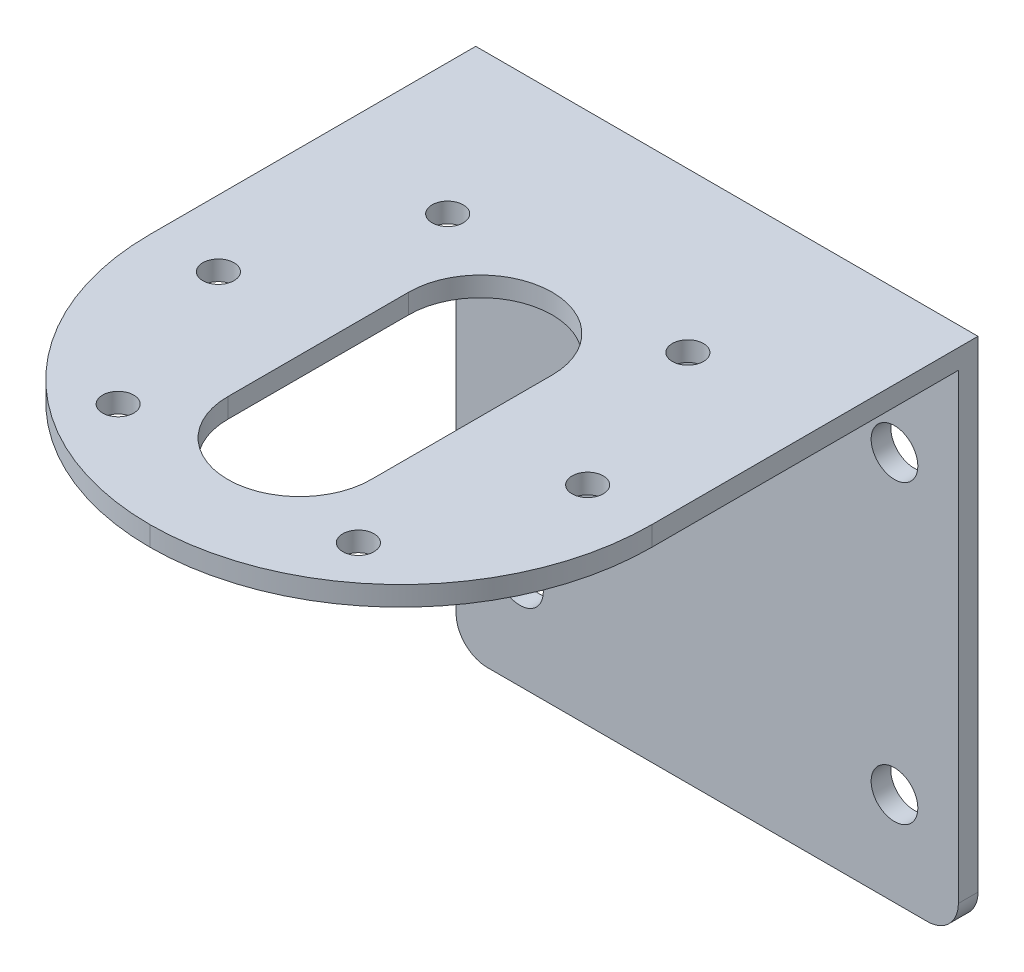
SolidWorks part; units mm, degrees
ref_plane "Front Plane" through (0, 0, 0) normal (0, 0, 1) x (1, 0, 0)
ref_plane "Top Plane" through (0, 0, 0) normal (0, 1, 0) x (1, 0, 0)
ref_plane "Right Plane" through (0, 0, 0) normal (1, 0, 0) x (0, 0, -1)
sketch "Sketch1" plane through (0, 0, 0) normal (0, 0, 1) x (1, 0, 0)
  line L1 (0, 0) -> (40.894, 0)
  line L2 (0, 0) -> (0, 40.132)
  line L3 (0, 40.132) -> (40.894, 40.132)
  line L4 (40.894, 0) -> (40.894, 40.132)
  dimension "D1" = 40.132
  dimension "D2" = 40.894
extrude "Boss-Extrude1" add sketch "Sketch1" along normal blind 1.6
sketch "Sketch2" plane through (0, 0, 1.6) normal (0, 0, 1) x (1, 0, 0)
  line L0 (40.894, 40.132) -> (0, 40.132) construction
  line L1 (0, 40.132) -> (0, 0) construction
  circle A0 centre (5.2, 31.732) radius 1.9
  circle A1 centre (5.2, 7.612) radius 1.9
  dimension "D1" = 3.8
  dimension "D2" = 8.4
  dimension "D3" = 5.2
  dimension "D4" = 5.2
  dimension "D5" = 24.12
extrude "Cut-Extrude1" cut sketch "Sketch2" against normal through all contours A1
sketch "Sketch3" plane through (0, 0, 1.6) normal (0, 0, 1) x (1, 0, 0)
extrude "Cut-Extrude2" cut sketch "Sketch2<3>" against normal through all
sketch "Sketch2<3>" plane through (0, 0, 1.6) normal (0, 0, 1) x (1, 0, 0) same geometry as "Sketch2"
ref_plane "Plane1" through (20.447, 0, 0) normal (-1, 0, 0) x (0, 0, 1)
mirror "Mirror2" about plane through (20.447, 0, 0) normal (-1, 0, 0) of "Cut-Extrude1", "Cut-Extrude2"
fillet "Fillet1" radius 2.54 2 edges at (40.894, 0, 0.8) (0, 0, 0.8)
sketch "Sketch5" plane through (0, 40.132, 0) normal (0, 1, 0) x (1, 0, 0)
  line L1 (40.894, 0) -> (0, 0)
  line L2 (40.894, 0) -> (40.894, -46.99)
  line L3 (40.894, -46.99) -> (0, -46.99)
  line L4 (0, 0) -> (0, -46.99)
  dimension "D1" = 46.99
extrude "Boss-Extrude2" add sketch "Sketch5" along normal blind 1.6
fillet "Fillet2" radius 20.447 2 edges at (0, 40.932, 46.99) (40.894, 40.932, 46.99)
sketch "Sketch6" plane through (0, 41.732, 0) normal (0, 1, 0) x (1, 0, 0)
  line L0 (40.894, 0) -> (0, 0) construction
  line L1 (40.894, -26.543) -> (40.894, 0) construction
  line L2 (30.226, -38.514) -> (30.226, -14.224) construction
  line L3 (30.226, -26.369) -> (40.8933, -26.369) construction
  circle A0 centre (30.226, -39.784) radius 1.27
  circle A1 centre (30.226, -12.954) radius 1.27
  circle A2 centre (35.48, -26.369) radius 1.27
  arc A3 (20.447, -46.99) -> (40.894, -26.543) centre (20.447, -26.543) ccw construction
  dimension "D1" = 2.54
  dimension "D2" = 12.954
  dimension "D3" = 10.668
  dimension "D4" = 26.83
  dimension "D5" = 5.414
extrude "Cut-Extrude3" cut sketch "Sketch6" against normal through all
mirror "Mirror3" about plane through (20.447, 0, 0) normal (-1, 0, 0) of "Cut-Extrude3"
sketch "Sketch7" plane through (0, 41.732, 0) normal (0, 1, 0) x (1, 0, 0)
  line L0 (20.447, -34.798) -> (20.447, -20.066) construction
  line L1 (20.447, 0.88) -> (20.447, -0.88) construction
  line L2 (14.605, -34.798) -> (14.605, -20.066)
  line L3 (26.289, -34.798) -> (26.289, -20.066)
  arc A0 (14.605, -34.798) -> (26.289, -34.798) centre (20.447, -34.798) ccw
  arc A1 (26.289, -20.066) -> (14.605, -20.066) centre (20.447, -20.066) ccw
  point P4 (20.447, -27.432)
  dimension "D1" = 5.842
  dimension "D2" = 14.732
  dimension "D3" = 12.192
extrude "Cut-Extrude4" cut sketch "Sketch7" against normal through all
equation "\"FoamCore\" = \".2\""
equation "\"MDF\" = \".2\""
equation "\"GMaterial\"= \".2\""
equation "\"PVCMountDiameter\" = \"0.5in\""
equation "\"PVCMountDistanceToEdge\" = \"0.5\""
equation "\"PVCThickness\" = \"0.13in\""
equation "\"BaseWidth\" = \"8in\""
equation "\"BaseLength\" = \"10in\""
equation "\"BallDiameter\" = \"38mm\""
equation "\"BaseGap\" = \"4in\""
equation "\"FunnelTopDiameter\" = \"8in\""
equation "\"FunnelTopDepth\" = \"0.5in\""
equation "\"BallGap\" = \"0.1in\""
equation "\"FunnelLength\" = 3in"
equation "\"FunnelMaterial\" = 0.1in"
equation "\"FunnelLowerDiameter\" = 1.9in"
equation "\"FunnelDepth\" = 1.5in"
equation "\"FunnelBendLength\" = 2*pi*\"FunnelLowerDiameter\"/2*135"
equation "\"AmmoFeederLength\" = 1.5in + 76mm"
equation "\"AmmoFeederCutoffLength\"= \"MovingWheelDiameter\""
equation "\"WheelThickness\" = 0.5in"
equation "\"LauncherWheelDiameter\" = 76mm"
equation "\"MotorFrontLength\" = 0.95in"
equation "\"MotorBodyTotalLength\" = 2.03in"
equation "\"MotorFrontDiameter\" = 1.5in"
equation "\"MotorLowerDriveshaftDiameter\" = 0.46in"
equation "\"MotorLowerDriveshaftThickness\" = 0.25in"
equation "\"MotorFullDriveshaftLength\" = 0.78in"
equation "\"MotorDriveshaftDiameter\" = 0.23in"
equation "\"MotorDriveshaftFlatThickness\" = 0.2in"
equation "\"MotorRearDiameter\" = 31.9mm"
equation "\"MotorDriveshaftBottomToTop\" = 31.1mm"
equation "\"MotorFlatDriveshaftLength\" = 11.7mm"
equation "\"MotorDistanceBetweenLowerandTopHoles\" = 0.5in"
equation "\"MotorMountsDistanceFromEdge\" = 0.06in"
equation "\"MotorScrewMountDiameter\" = 0.1in"
equation "\"MotorScrewMountDepth\" = 0.13in"
equation "\"HBRidgeScrewHoleDeep\" = 0.18in"
equation "\"MotorMountWidth\" = \"1.61in\""
equation "\"MotorMountLength\" = \"1.58in\""
equation "\"MotorMountToEdgeGap\" = \"3.3mm\""
equation "\"MotorMountToInsideEdgeGap\" = \"6.5mm\""
equation "\"MotorMountToMountWidthGap\" = \"25.8mm\""
equation "\"MotorMountToMountLengthGap\" = \"20.5mm\""
equation "\"HBridgeWidth\" = 2.25in"
equation "\"HBridgeLength\" = 1.40in"
equation "\"UnoWidth\" = 3.13in"
equation "\"UnoLength\" = 3.06in"
equation "\"BatteryWidth\" = 1.15in"
equation "\"BatteryLength\" = 3.86in"
equation "\"ScrewDiameter\" = 2.7mm"
equation "\"D1@Sketch1\"=\"MotorMountLength\""
equation "\"D2@Sketch1\"=\"MotorMountWidth\""
equation "\"MotorMountMaterialThickness\" = 1.6mm"
equation "\"D1@Boss-Extrude1\"=\"MotorMountMaterialThickness\""
equation "\"D1@Sketch2\"=\"MotorMountBaseScrewholeDiameter\""
equation "\"MotorMountBaseScrewholeDiameter\" = 3.8mm"
equation "\"D2@Sketch2\"=\"MotorMountToInsideEdgeGap\"+\"MotorMountBaseScrewholeDiameter\"/2"
equation "\"D3@Sketch2\"=\"MotorMountToEdgeGap\"+\"MotorMountBaseScrewholeDiameter\"/2"
equation "\"D4@Sketch2\"=\"MotorMountToEdgeGap\"+\"MotorMountBaseScrewholeDiameter\"/2"
equation "\"MotorMountBaseDistancebetweenHoles\" = 0.8in"
equation "\"D5@Sketch2\"=\"MotorMountBaseDistancebetweenHoles\"+\"MotorMountBaseScrewholeDiameter\""
equation "\"MotorMountHeight\" = 1.85in"
equation "\"D1@Sketch5\"=\"MotorMountHeight\""
equation "\"D1@Boss-Extrude2\"=\"MotorMountMaterialThickness\""
equation "\"D1@Fillet2\"=\"MotorMountWidth\"/2"
equation "\"D1@Sketch6\"=\"MotorScrewMountDiameter\""
equation "\"MotorMountFaceScrewtoBase\" = 0.46in"
equation "\"MotorMountFaceDistanceBetweenScrews\" = 0.95in"
equation "\"MotorMountFaceMiddletoEdge\" = 0.16in"
equation "\"D2@Sketch6\"=\"MotorMountFaceScrewtoBase\"+\"MotorScrewMountDiameter\"/2"
equation "\"MotorMountFaceBottomtoEdge\" = 0.42in"
equation "\"D3@Sketch6\"=\"MotorMountFaceBottomtoEdge\""
equation "\"D4@Sketch6\"=\"MotorMountFaceDistanceBetweenScrews\"+\"ScrewDiameter\""
equation "\"D5@Sketch6\"=\"MotorMountFaceMiddletoEdge\"+\"ScrewDiameter\"/2"
equation "\"D1@Sketch7\"=\"MotorLowerDriveshaftDiameter\"/2"
equation "\"MotorMountCenterholeHeight\" = 1.04in"
equation "\"D2@Sketch7\"=\"MotorMountCenterholeHeight\"-\"MotorLowerDriveshaftDiameter\""
equation "\"MotorMountCenterholetoEdge\" = 0.25in"
equation "\"D3@Sketch7\"=\"MotorMountCenterholetoEdge\"+\"MotorLowerDriveshaftDiameter\"/2"
